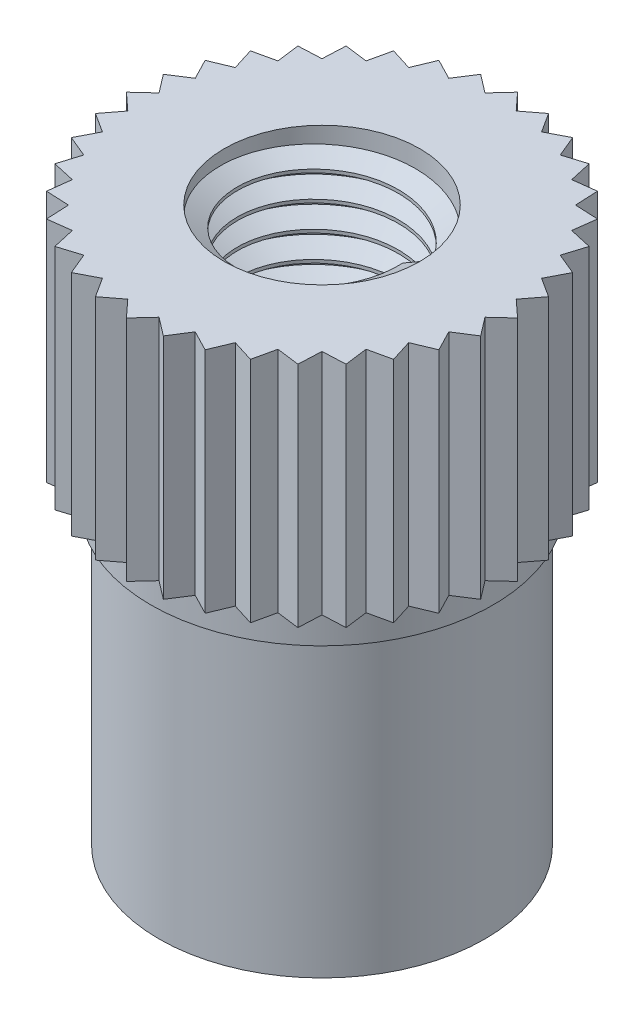
SolidWorks part; units mm, degrees
ref_plane "Alzado" through (0, 0, 0) normal (0, 0, 1) x (1, 0, 0)
ref_plane "Planta" through (0, 0, 0) normal (0, 1, 0) x (1, 0, 0)
ref_plane "Vista lateral" through (0, 0, 0) normal (1, 0, 0) x (0, 0, -1)
sketch "Croquis2" plane through (0, 0, 0) normal (0, 1, 0) x (1, 0, 0)
  circle A0 centre (0, 0) radius 3
  circle A1 centre (0, 0) radius 2.5
  circle A2 centre (0, 0) radius 1.5
  dimension "D1" = 6
  dimension "D2" = 5
  dimension "D3" = 3
extrude "Saliente-Extruir1" add sketch "Croquis2" along normal blind 8.5 contours A0
extrude "Cortar-Extruir1" cut sketch "Croquis2<3>" along normal blind 5 contours A0 A1 | A2 region at (-2.9151, 0, 0) region at (0, 0, 0)
sketch "Croquis2<3>" plane through (0, 0, 0) normal (0, 1, 0) x (1, 0, 0) same geometry as "Croquis2"
sketch "Croquis4" plane through (0, 8.5, 0) normal (0, 1, 0) x (1, 0, 0)
  line L0 (0, 0) -> (-3, 0)
  line L1 (0, 0) -> (-4.8666, 0.4258)
  line L2 (0, 0) -> (-4.6376, 0.8177)
  line L3 (-2.7395, 0.2397) -> (-3, 0)
  line L4 (-2.7395, 0.2397) -> (-2.9544, 0.5209)
  circle A0 centre (0, 0) radius 2.75
  circle A1 centre (0, 0) radius 3 construction
  circle A2 centre (0, 0) radius 3
  point P8 (-2.9544, 0.5209)
  dimension "D1" = 5.5
  dimension "D2" = 5
  dimension "D3" = 10
extrude "Cortar-Extruir3" cut sketch "Croquis4" against normal through all contours L3 L1 | L1 L4 L3 region at (-2.9107, 8.5, -0.1665) region at (-2.8954, 8.5, -0.3415)
pattern_circular "MatrizC2" count 37 every 10 about axis through (0, 5, 0) along (0, -1, 0) of "Cortar-Extruir3"
sketch "Croquis5" plane through (0, 5, 0) normal (0, -1, 0) x (1, 0, 0)
  circle A0 centre (0, 0) radius 2.625
  dimension "D1" = 5.25
extrude "Saliente-Extruir2" add sketch "Croquis5" along normal blind 0.5
hole_wizard "Perforador para roscar para macho de roscar para M21" positions "Croquis7" profile "Croquis9" hole size "M2" standard "ISO"
sketch "Croquis7" plane through (0, 8.5, 0) normal (0, 1, 0) x (1, 0, 0)
  point P0 (0, 0)
sketch "Croquis9" plane through (0, 8.5, 0) normal (1, 0, 0) x (0, 0, 1)
  line L0 (0, 0) -> (0, 3)
  line L1 (0, 3) -> (1.5, 3)
  line L2 (1.5, 3) -> (1.5, 0)
  line L5 (1.5, 0) -> (0, 0)
  line L10 (0, 3) -> (-1.5, 3) construction
  line L11 (0, -6.35) -> (0, 107.95) construction
  dimension "Diámetro de taladro" = 3
  dimension "Profundidad de taladro" = 3
  dimension "Ángulo de perforador" = 180
sketch "Croquis13" plane through (0, 8.5, 0) normal (0, 1, 0) x (1, 0, 0)
  circle A0 centre (0, 0) radius 1.5
  circle A1 centre (0, 0) radius 1.5 construction
curve "Hélice/Espiral1" pitch 0.4 height 3 radius 1.5 centre (0, 8.5, 0) axis (0, -1, 0) start towards (1, 0, 0)
sketch "Croquis16" plane through (0, 0, 0) normal (0, 0, 1) x (1, 0, 0)
  line L0 (0, 0) -> (0, 8.5)
  line L1 (0, 8.5) -> (1.5, 8.5)
  line L2 (1.5, 8.5) -> (-1.5, 8.5) construction
  line L3 (1.5, 8.5) -> (1.2402, 8.35)
  line L4 (1.2402, 8.35) -> (1.2402, 8.3)
  line L5 (1.2402, 8.3) -> (1.5, 8.15)
  line L6 (1.5, 8.5) -> (1.5, 8.15)
  line L7 (1.5, 8.325) -> (1.2402, 8.325) construction
  line L8 (1.3701, 8.425) -> (1.3701, 8.225) construction
  point P3 (0, 0)
sweep "Barrer1" add profiles "Croquis16" path "Hélice/Espiral1"
